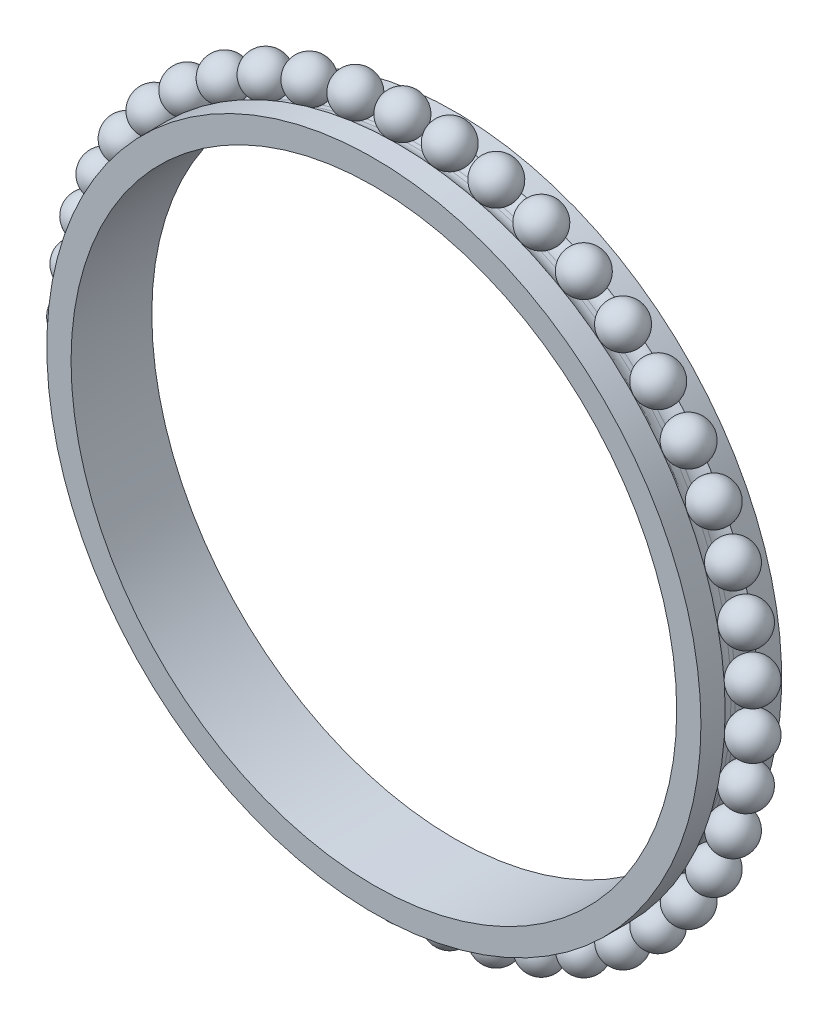
SolidWorks part; units mm, degrees
ref_plane "前视基准面" through (0, 0, 0) normal (0, 0, 1) x (1, 0, 0)
ref_plane "上视基准面" through (0, 0, 0) normal (0, 1, 0) x (1, 0, 0)
ref_plane "右视基准面" through (0, 0, 0) normal (1, 0, 0) x (0, 0, -1)
sketch "草图1" plane through (0, 0, 0) normal (0, 0, 1) x (1, 0, 0)
  circle A0 centre (0, 0) radius 37.5
  circle A5 centre (0, 0) radius 39.5
extrude "凸台-拉伸4" add sketch "草图1" along normal blind 10
ref_plane "基准面5" through (0, 0, 5) normal (0, 0, 1) x (1, 0, 0)
sketch "草图4" plane through (0, 0, 5) normal (0, 0, 1) x (1, 0, 0)
  line L0 (-42, 2.5) -> (-42, -2.5)
  arc A1 (-42, -2.5) -> (-42, 2.5) centre (-42, 0) ccw
revolve "旋转1" add sketch "草图4" angle 360 about L0
sketch "草图5" plane through (0, 0, 10) normal (0, 0, 1) x (1, 0, 0)
  circle A0 centre (0, 0) radius 40.5
  circle A1 centre (0, 0) radius 39.5
extrude "凸台-拉伸5" add sketch "草图5" against normal blind 3
fillet "圆角1" radius 2 1 edges at (39.5, 0, 7)
sketch "草图6" plane through (0, 0, 0) normal (0, 0, -1) x (-1, 0, 0)
  circle A0 centre (0, 0) radius 40.5
  circle A1 centre (0, 0) radius 39.5
extrude "凸台-拉伸9" add sketch "草图6" against normal blind 3
fillet "圆角2" radius 2 1 edges at (-39.5, 0, 3)
pattern_circular "阵列(圆周)1" count 45 every 8 about axis through (0, 0, 3) along (0, 0, -1) of bodies 105
